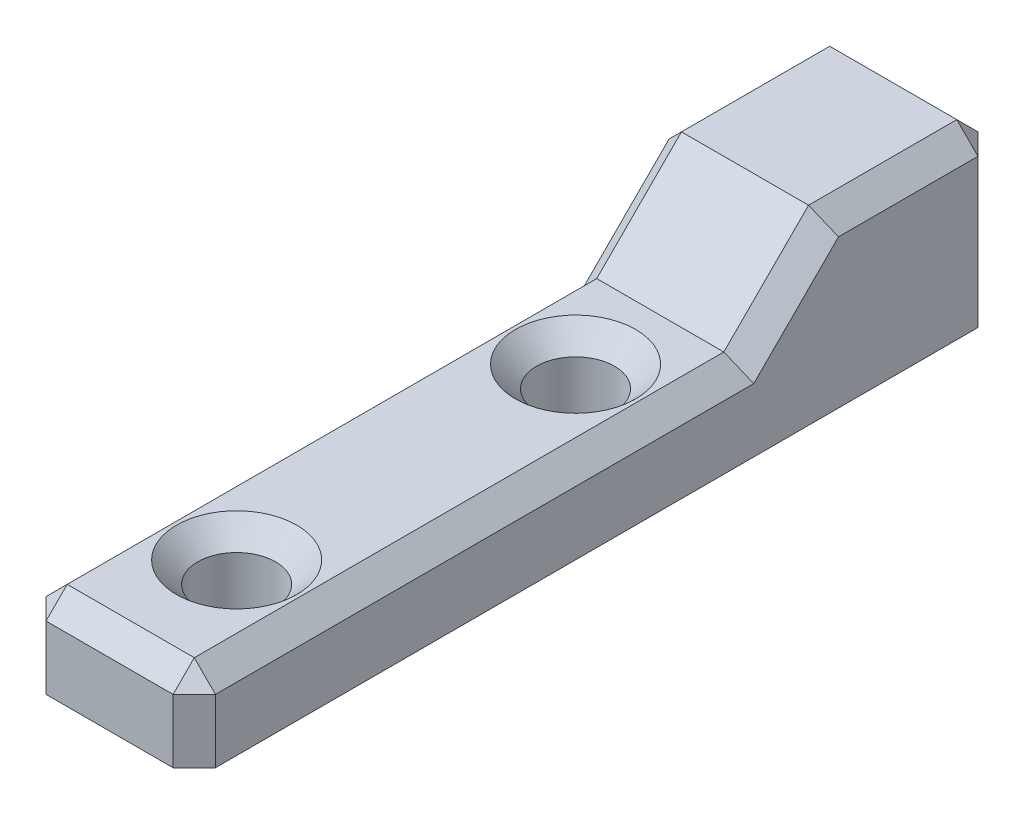
SolidWorks part; units mm, degrees
ref_plane "Front Plane" through (0, 0, 0) normal (0, 0, 1) x (1, 0, 0)
ref_plane "Top Plane" through (0, 0, 0) normal (0, 1, 0) x (1, 0, 0)
ref_plane "Right Plane" through (0, 0, 0) normal (1, 0, 0) x (0, 0, -1)
sketch "Sketch1" plane through (0, 0, 0) normal (0, 1, 0) x (1, 0, 0)
  line L1 (0, 0) -> (12.7, 0)
  line L2 (0, 0) -> (0, 60.325)
  line L3 (0, 60.325) -> (12.7, 60.325)
  line L4 (12.7, 0) -> (12.7, 60.325)
  circle A0 centre (6.35, 9.525) radius 2.921
  circle A1 centre (6.35, 34.925) radius 2.921
  dimension "D3" = 5.842
  dimension "D1" = 12.7
  dimension "0.375" = 9.525
  dimension "D4" = 25.4
  dimension "D5" = 25.4
extrude "Boss-Extrude1" add sketch "Sketch1" along normal blind 12.7
sketch "Sketch2" plane through (12.7, 0, 0) normal (1, 0, 0) x (0, 0, -1)
  line L0 (60.325, 12.7) -> (60.325, 0) construction
  line L1 (0, 12.7) -> (47.625, 12.7)
  line L2 (0, 12.7) -> (0, 6.35)
  line L3 (0, 6.35) -> (47.625, 6.35)
  line L4 (47.625, 12.7) -> (47.625, 6.35)
  dimension "D1" = 12.7
  dimension "D2" = 6.35
extrude "Cut-Extrude1" cut sketch "Sketch2" against normal through all
chamfer "Chamfer1" distance 6.35 angle 45 1 edges at (6.35, 6.35, -47.625)
chamfer "Chamfer2" distance 1.5875 angle 45 14 edges at (0, 3.175, 0) (12.7, 3.175, 0) (0, 6.35, -60.325) (12.7, 6.35, -60.325) (0, 9.525, -44.45) (0, 12.7, -53.975) (6.35, 12.7, -60.325) (12.7, 12.7, -53.975) (12.7, 9.525, -44.45) (0, 6.35, -20.6375) (6.35, 6.35, 0) (12.7, 6.35, -20.6375) (6.35, 6.35, -12.446) (6.35, 6.35, -37.846)
